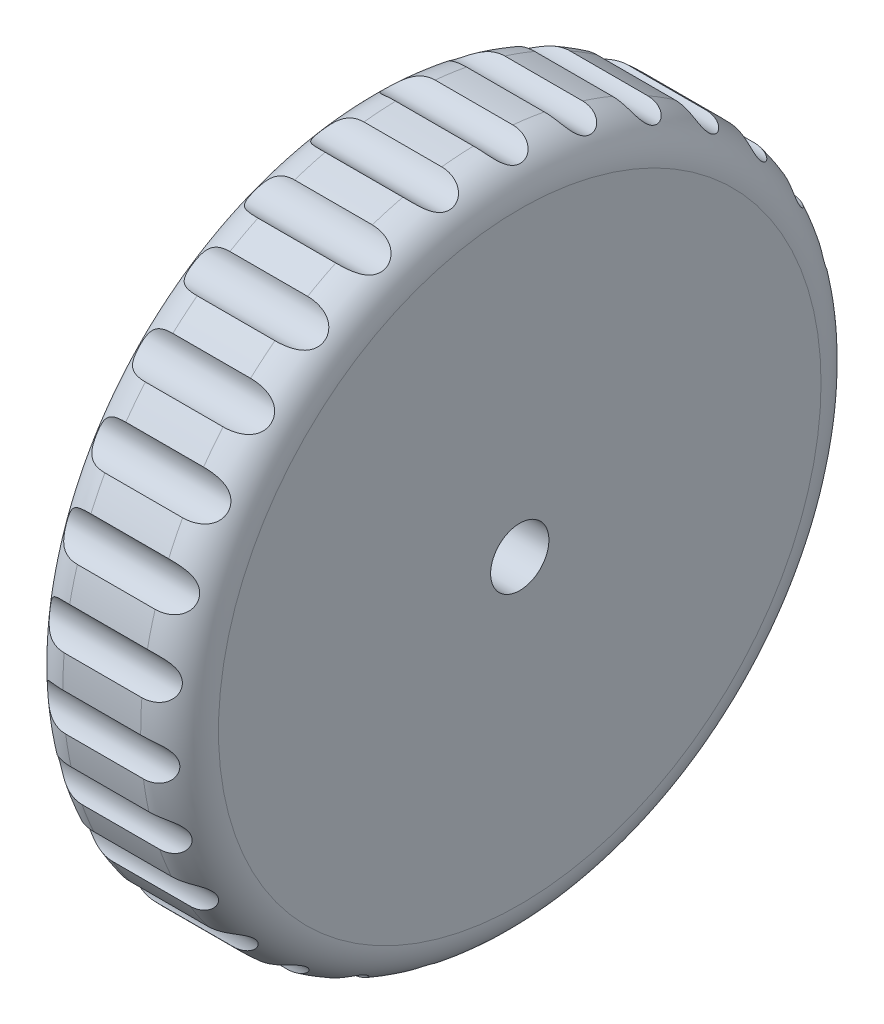
SolidWorks part; units mm, degrees
ref_plane "Ön Düzlem" through (0, 0, 0) normal (0, 0, 1) x (1, 0, 0)
ref_plane "Üst Düzlem" through (0, 0, 0) normal (0, 1, 0) x (1, 0, 0)
ref_plane "Sağ Düzlem" through (0, 0, 0) normal (1, 0, 0) x (0, 0, -1)
sketch "Sketch1" plane through (0, 0, 0) normal (1, 0, 0) x (0, 0, -1)
  circle A0 centre (-45.9945, -4.928) radius 175
extrude "Boss-Extrude1" add sketch "Sketch1" along normal blind 40 and the other way blind 40
fillet "Fillet1" radius 20 2 edges at (40, -4.928, -129.0055) (-40, -4.928, -129.0055)
sketch "Sketch2" plane through (0, 0, 0) normal (1, 0, 0) x (0, 0, -1)
  circle A0 centre (-176.4023, 121.2985) radius 12.2077
extrude "Cut-Extrude1" cut sketch "Sketch2" against normal blind 40 and the other way blind 40
pattern_circular "CirPattern1" count 30 over 360 about axis through (-40, -4.928, 45.9945) along (1, 0, 0) of "Cut-Extrude1"
sketch "Sketch3" plane through (0, 0, 0) normal (1, 0, 0) x (0, 0, -1)
  circle A0 centre (-45.9945, -4.928) radius 15
extrude "Cut-Extrude2" cut sketch "Sketch3" against normal blind 40 and the other way blind 40
